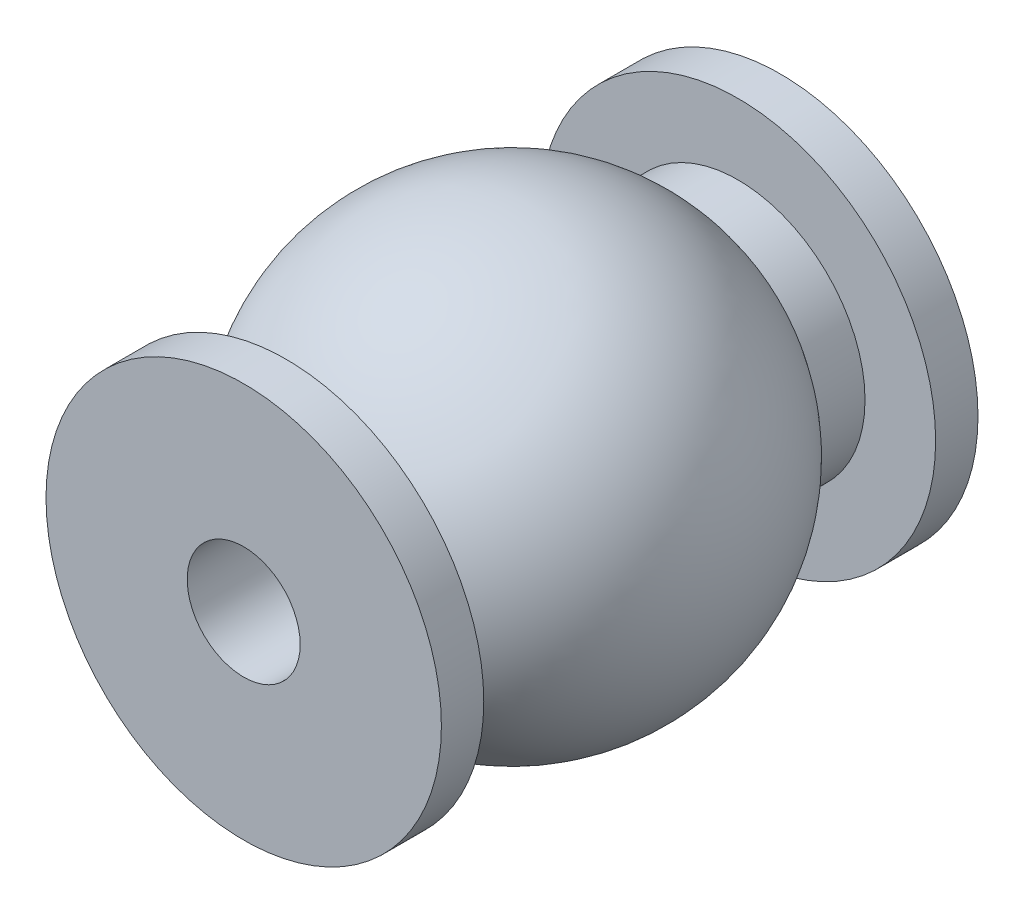
SolidWorks part; units mm, degrees
ref_plane "Front Plane" through (0, 0, 0) normal (0, 0, 1) x (1, 0, 0)
ref_plane "Top Plane" through (0, 0, 0) normal (0, 1, 0) x (1, 0, 0)
ref_plane "Right Plane" through (0, 0, 0) normal (1, 0, 0) x (0, 0, -1)
sketch "Sketch1" plane through (0, 0, 0) normal (0, 1, 0) x (1, 0, 0)
  line L0 (-4.5, -6.3097) -> (-4.5, -8)
  line L2 (-4.5, 8) -> (-4.5, 6.3097)
  line L3 (0, -9.5) -> (0, 9.5)
  line L7 (-7, 8) -> (-4.5, 8)
  line L8 (-7, 8) -> (-7, 9.5)
  line L9 (-7, 9.5) -> (0, 9.5)
  line L11 (-7, -8) -> (-4.5, -8)
  line L12 (-7, -8) -> (-7, -9.5)
  line L13 (-7, -9.5) -> (0, -9.5)
  arc A0 (-4.5, 6.3097) -> (-4.5, -6.3097) centre (0, 0) ccw
  point P14 (-7, 8.75)
  dimension "D1" = 15.5
  dimension "D3" = 4.5
  dimension "D4" = 16
  dimension "D7" = 7
  dimension "D8" = 1.5
  dimension "D9" = 1.5
  dimension "D11" = 7
revolve "Revolve1" add sketch "Sketch1" angle 360 about L3
hole_wizard "Ø4.0 (4) Diameter Hole1" positions "Sketch3" profile "Sketch2" hole size "Ø4.0" standard "ANSI Metric" end condition through all
sketch "Sketch3" plane through (0, 0, 9.5) normal (0, 0, 1) x (1, 0, 0)
  point P0 (0, 0)
sketch "Sketch2" plane through (0, 0, 9.5) normal (1, 0, 0) x (0, -1, 0)
  line L0 (0, 0) -> (0, 19)
  line L1 (0, 19) -> (2, 19)
  line L2 (2, 19) -> (2, 0)
  line L5 (2, 0) -> (0, 0)
  line L11 (0, -6.35) -> (0, 107.95) construction
  dimension "Thru Hole Dia." = 4
  dimension "Thru Hole Depth" = 19
